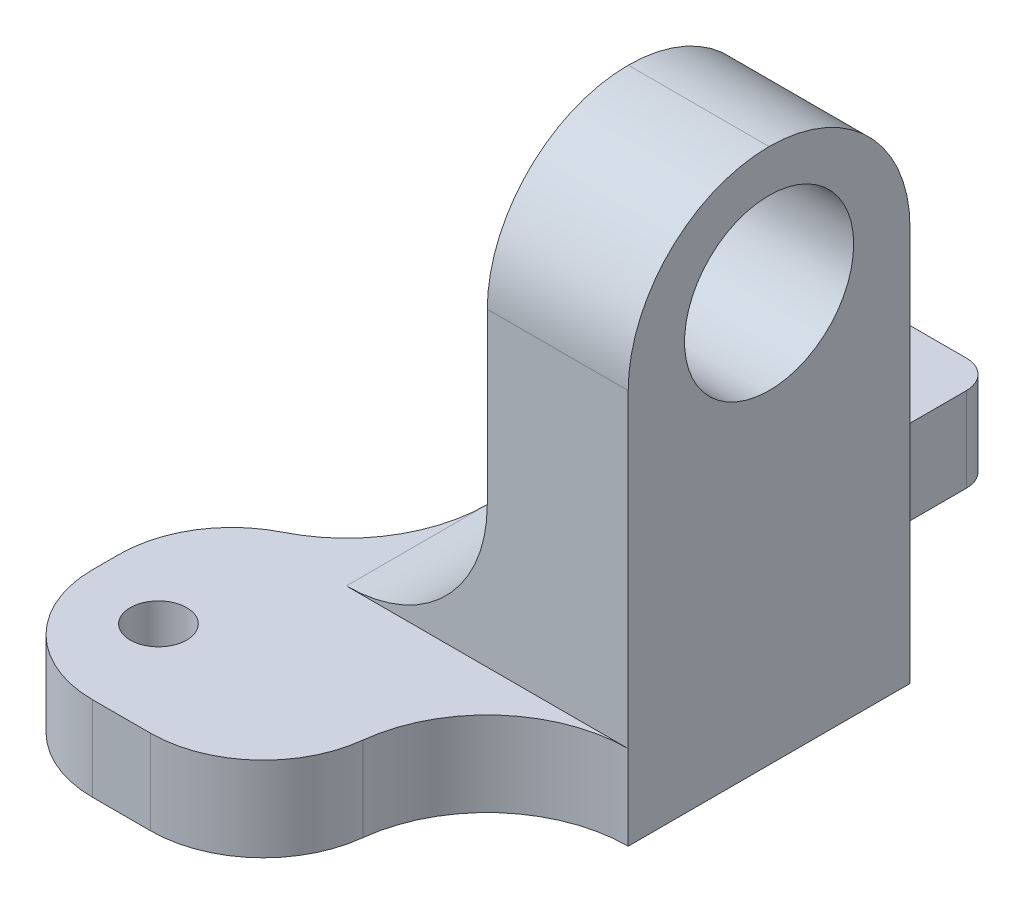
SolidWorks part; units mm, degrees
ref_plane "Front Plane" through (0, 0, 0) normal (0, 0, 1) x (1, 0, 0)
ref_plane "Top Plane" through (0, 0, 0) normal (0, 1, 0) x (1, 0, 0)
ref_plane "Right Plane" through (0, 0, 0) normal (1, 0, 0) x (0, 0, -1)
sketch "Sketch1" plane through (0, 0, 0) normal (0, 1, 0) x (1, 0, 0)
  line L1 (-35.5002, -13) -> (-20.5002, -13)
  line L2 (-35.5002, -13) -> (-35.5002, 13)
  line L3 (-35.5002, 13) -> (-20.5002, 13)
  line L4 (-20.5002, -13) -> (-20.5002, 13)
  point P0 (-20.5002, 0)
  dimension "D1" = 26
  dimension "D2" = 15
extrude "Boss-Extrude1" add sketch "Sketch1" along normal blind 3 contours L2 L1 L4 L3
sketch "Sketch2" plane through (0, 3, 0) normal (0, 1, 0) x (1, 0, 0)
  line L0 (-35.5002, 13) -> (-20.5002, 13) construction
  line L1 (-35.5002, -13) -> (-35.5002, 13) construction
  circle A0 centre (-32.6667, -9.5) radius 1
  circle A1 centre (-28, 10.5) radius 1
  dimension "D1" = 2
  dimension "D2" = 2
  dimension "D3" = 2.5
  dimension "D4" = 20
  dimension "D5" = 4.6667
  dimension "D6" = 2.8335
extrude "Cut-Extrude1" cut sketch "Sketch2" against normal up to next
sketch "Sketch3" plane through (0, 3, 0) normal (0, 1, 0) x (1, 0, 0)
  line L0 (-20.5002, -13) -> (-20.5002, 13) construction
  line L1 (-20.5002, 5) -> (-25.5002, 5)
  line L2 (-20.5002, 5) -> (-20.5002, -5)
  line L3 (-20.5002, -5) -> (-25.5002, -5)
  line L4 (-25.5002, 5) -> (-25.5002, -5)
  point P6 (-20.5002, 0)
  point P7 (-20.5002, 0)
  dimension "D1" = 5
  dimension "D2" = 10
extrude "Boss-Extrude2" add sketch "Sketch3" along normal blind 16
sketch "Sketch4" plane through (-20.5002, 0, 0) normal (1, 0, 0) x (0, 0, -1)
  line L1 (-13, 0) -> (13, 0) construction
  line L2 (-5, 19) -> (5, 19) construction
  circle A0 centre (0, 14.5) radius 3
  point P10 (0, 0)
  dimension "D1" = 6
  dimension "D2" = 4.5
extrude "Cut-Extrude2" cut sketch "Sketch4" against normal up to next contours A0
sketch "Sketch5" plane through (0, 3, 0) normal (0, 1, 0) x (1, 0, 0)
  line L0 (-20.5002, 5) -> (-25.5002, 5) construction
  line L1 (-20.5002, 13) -> (-25.5002, 13)
  line L2 (-20.5002, 13) -> (-20.5002, 5)
  line L3 (-20.5002, 5) -> (-25.5002, 5)
  line L4 (-25.5002, 13) -> (-25.5002, 5)
  line L5 (-35.5002, 13) -> (-30.5002, 13)
  line L6 (-35.5002, 13) -> (-35.5002, -5)
  line L7 (-35.5002, -5) -> (-30.5002, -5)
  line L8 (-30.5002, 13) -> (-30.5002, -5)
  line L9 (-20.5002, -13) -> (-25.5002, -13)
  line L10 (-20.5002, -13) -> (-20.5002, -5)
  line L11 (-20.5002, -5) -> (-25.5002, -5)
  line L12 (-25.5002, -13) -> (-25.5002, -5)
  line L13 (-25.5002, 5) -> (-25.5002, -5) construction
  dimension "D1" = 5
extrude "Cut-Extrude3" cut sketch "Sketch5" against normal up to next
fillet "Fillet1" radius 5 2 edges at (-23.0002, 19, -5) (-23.0002, 19, 5)
fillet "Fillet2" radius 5 1 edges at (-25.5002, 3, 0)
fillet "Fillet3" radius 5 3 edges at (-30.5002, 1.5, 5) (-25.5002, 1.5, -5) (-25.5002, 1.5, 5)
fillet "Fillet4" radius 4 3 edges at (-35.5002, 1.5, 5) (-35.5002, 1.5, 13) (-25.5002, 1.5, 13)
fillet "Fillet5" radius 1 2 edges at (-25.5002, 1.5, -13) (-30.5002, 1.5, -13)
equation "\"D2@Sketch2\"=\"D1@Sketch2\""
